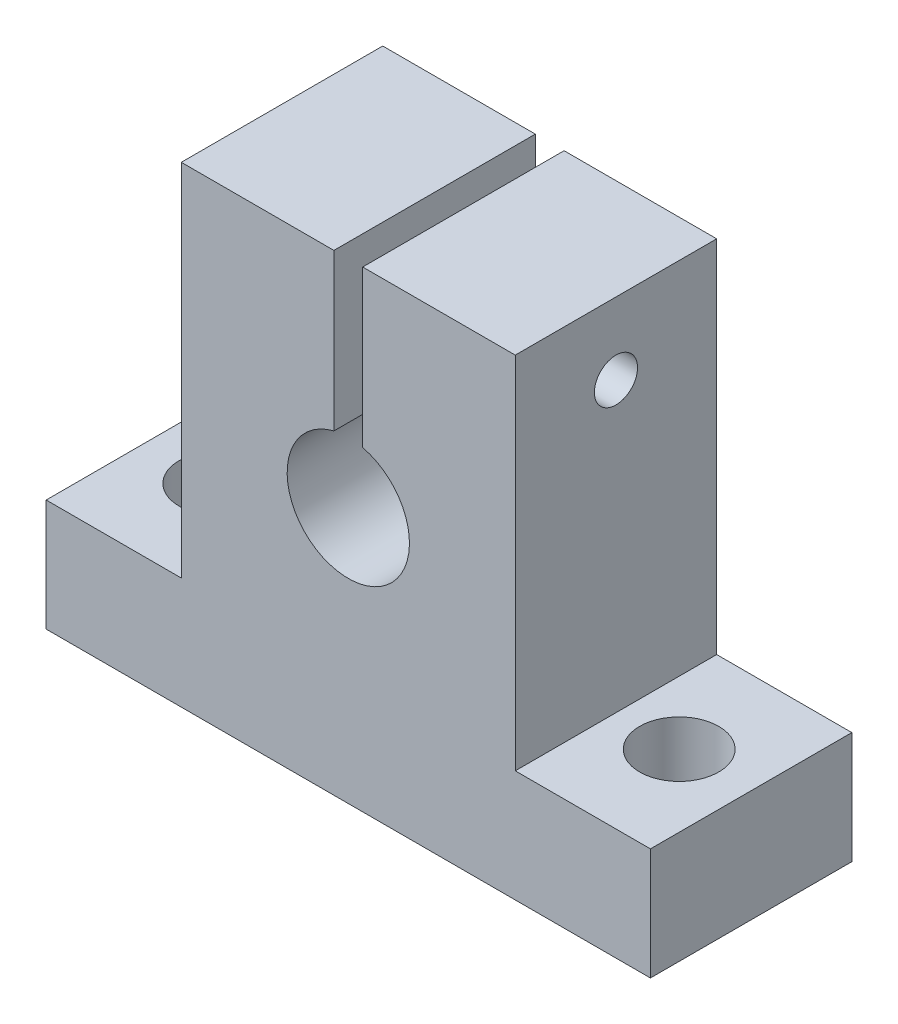
SolidWorks part; units mm, degrees
material "AISI 304"
ref_plane "Front Plane" through (0, 0, 0) normal (0, 0, 1) x (1, 0, 0)
ref_plane "Top Plane" through (0, 0, 0) normal (0, 1, 0) x (1, 0, 0)
ref_plane "Right Plane" through (0, 0, 0) normal (1, 0, 0) x (0, 0, -1)
sketch "Sketch1" plane through (0, 0, 0) normal (0, 0, 1) x (1, 0, 0)
  line L0 (0, 0) -> (42, 0)
  line L1 (42, 0) -> (42, 7.7738)
  line L2 (42, 7.7738) -> (32.6062, 7.7738)
  line L3 (32.6062, 7.7738) -> (32.6062, 32.8)
  line L4 (9.3938, 32.8) -> (20, 32.8)
  line L5 (9.3938, 32.8) -> (9.3938, 7.7738)
  line L6 (9.3938, 7.7738) -> (0, 7.7738)
  line L7 (0, 7.7738) -> (0, 0)
  line L8 (20, 32.8) -> (20, 17.8)
  line L9 (20, 17.8) -> (22, 17.8)
  line L10 (22, 17.8) -> (22, 32.8)
  line L11 (22, 32.8) -> (32.6062, 32.8)
  dimension "D1" = 42
  dimension "D2" = 32.8
  dimension "D3" = 2
  dimension "D4" = 15
extrude "Boss-Extrude1" add sketch "Sketch1" along normal blind 14
sketch "Sketch2" plane through (0, 0, 14) normal (0, 0, 1) x (1, 0, 0)
  line L0 (22, 17.8) -> (20, 17.8) construction
  circle A0 centre (21, 17.8) radius 4.25
  dimension "D1" = 8.5
extrude "Cut-Extrude1" cut sketch "Sketch2" against normal through all
sketch "Sketch3" plane through (0, 7.7738, 0) normal (0, 1, 0) x (1, 0, 0)
  line L0 (5, -7) -> (37, -7) construction
  line L5 (9.3938, 0) -> (0, 0) construction
  line L6 (0, -14) -> (0, 0) construction
  circle A0 centre (5, -7) radius 2.75
  circle A1 centre (37, -7) radius 2.75
  dimension "D1" = 5.5
  dimension "D2" = 32
  dimension "D3" = 7
  dimension "D4" = 5
extrude "Cut-Extrude2" cut sketch "Sketch3" against normal through all
sketch "Sketch4" plane through (32.6062, 0, 0) normal (1, 0, 0) x (0, 0, -1)
  line L0 (-14, 32.8) -> (0, 32.8) construction
  line L1 (0, 7.7738) -> (0, 32.8) construction
  circle A0 centre (-7, 27.8) radius 1.5
  dimension "D1" = 3
  dimension "D3" = 7
  dimension "D2" = 5
extrude "Cut-Extrude3" cut sketch "Sketch4" against normal through all
